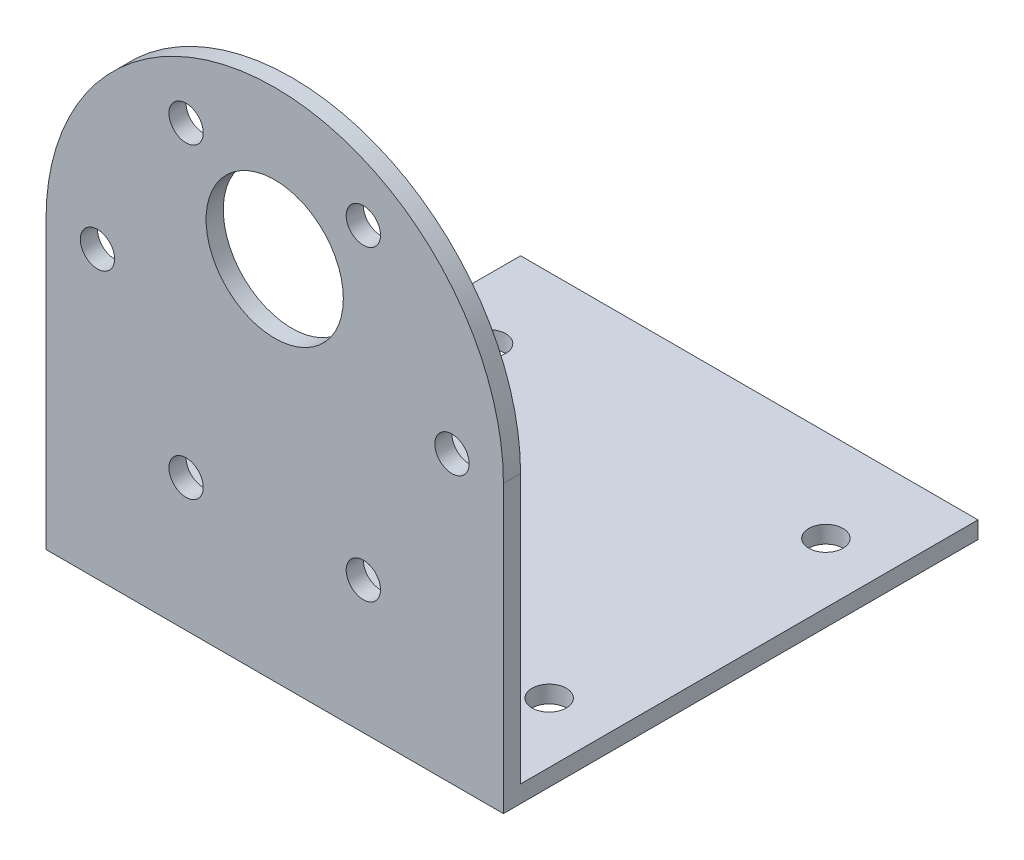
SolidWorks part; units mm, degrees
ref_plane "前视基准面" through (0, 0, 0) normal (0, 0, 1) x (1, 0, 0)
ref_plane "上视基准面" through (0, 0, 0) normal (0, 1, 0) x (1, 0, 0)
ref_plane "右视基准面" through (0, 0, 0) normal (1, 0, 0) x (0, 0, -1)
sketch "草图1" plane through (0, 0, 0) normal (0, 0, 1) x (1, 0, 0)
  line L0 (-20, 0) -> (-20, -25)
  line L1 (20, 0) -> (20, -25)
  line L2 (20, -25) -> (-20, -25)
  line L3 (-20, -25) -> (-19.9632, -25.1555)
  line L5 (20, -25) -> (-20, -25)
  line L6 (20, -25) -> (20, -23.5)
  line L7 (20, -23.5) -> (-20, -23.5)
  line L8 (-20, -25) -> (-20, -23.5)
  circle A0 centre (0, 0) radius 18.5 construction
  circle A1 centre (0, 0) radius 15.5 construction
  circle A2 centre (-15.5, 0) radius 1.5
  circle A3 centre (-7.75, 13.4234) radius 1.5
  circle A4 centre (7.75, 13.4234) radius 1.5
  circle A5 centre (15.5, 0) radius 1.5
  circle A6 centre (7.75, -13.4234) radius 1.5
  circle A7 centre (-7.75, -13.4234) radius 1.5
  arc A8 (20, 0) -> (-20, 0) centre (0, 0) ccw
  circle A9 centre (0, 7) radius 6
  point P18 (0, 0)
  dimension "D1" = 37
  dimension "D2" = 31
  dimension "D3" = 3
  dimension "D5" = 40
  dimension "D7" = 12
  dimension "D6" = 25
  dimension "D8" = 7
  dimension "D9" = 1.5
  dimension "D4" = 6
extrude "凸台-拉伸1" add sketch "草图1" along normal blind 1.5 contours L1 A8 L0 L2 A9 A2 A3 A4 A5 A6 A7 | L1 L7 L0 L2 region at (0, -4.6031, 0) region at (0, -24.25, 0)
extrude "凸台-拉伸2" add sketch "草图1<3>" against normal blind 40 contours L1 L7 L0 L2 region at (0, -24.25, 0)
sketch "草图1<3>" plane through (0, 0, 0) normal (0, 0, 1) x (1, 0, 0) same geometry as "草图1"
sketch "草图2" plane through (0, -23.5, 0) normal (0, 1, 0) x (1, 0, 0)
  line L0 (-20, 40) -> (-20, 0) construction
  line L1 (20, 40) -> (-20, 40) construction
  line L2 (0, 40) -> (0, 0) construction
  circle A0 centre (-14.75, 31.95) radius 1.5
  circle A1 centre (-14.75, 7.75) radius 1.5
  circle A2 centre (14.75, 7.75) radius 1.5
  circle A3 centre (14.75, 31.95) radius 1.5
  dimension "D1" = 3
  dimension "D2" = 5.25
  dimension "D3" = 8.05
  dimension "D4" = 3
  dimension "D5" = 24.2
extrude "切除-拉伸1" cut sketch "草图2" against normal through all
